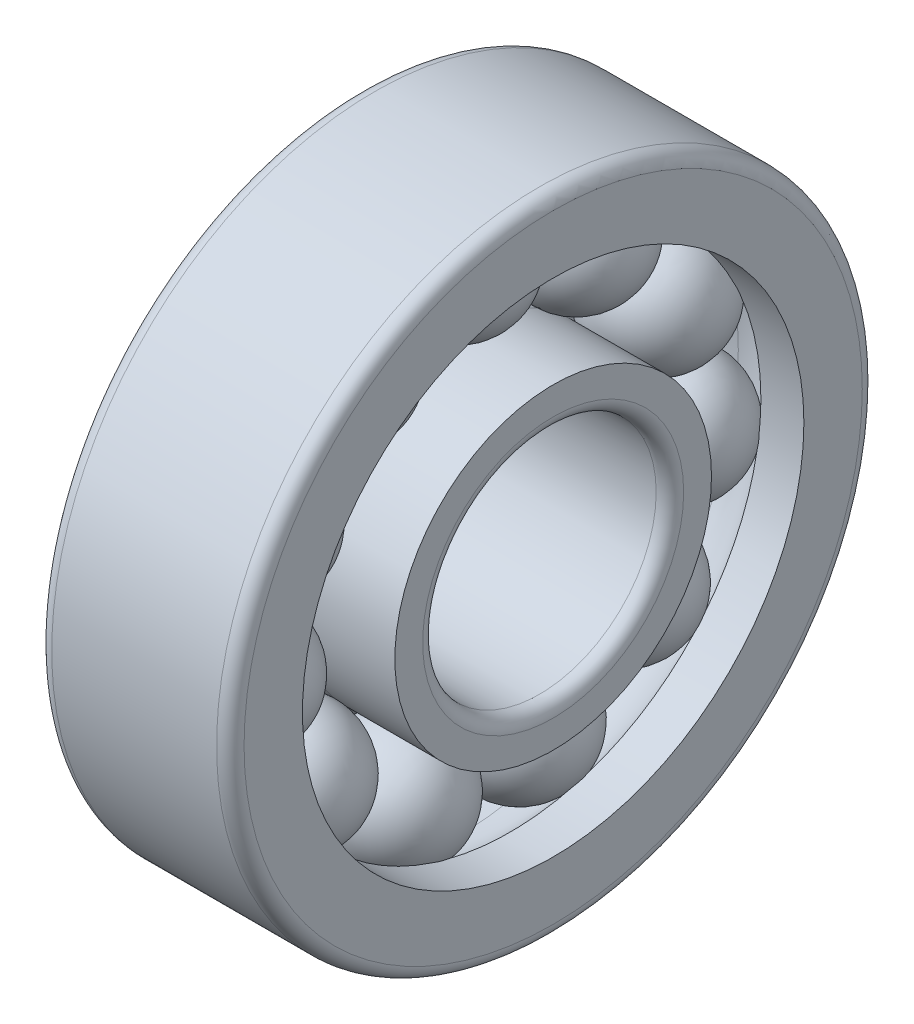
SolidWorks part; units mm, degrees
ref_plane "Plane1" through (0, 0, 0) normal (0, 0, 1) x (1, 0, 0)
ref_plane "Plane2" through (0, 0, 0) normal (0, 1, 0) x (1, 0, 0)
ref_plane "Plane3" through (0, 0, 0) normal (1, 0, 0) x (0, 0, -1)
sketch "Clipboard" plane through (0, 0, 0) normal (0, 0, 1) x (1, 0, 0)
  line L0 (-10, 0) -> (10, 0) construction
  line L1 (0, 0) -> (21.9499, -4.2666)
  line L2 (0, 0) -> (15.9976, -0.2792)
  line L3 (0, 0) -> (22.3573, 0.3902)
  line L4 (0, 0) -> (-22.3573, -0.3902)
  dimension "BallCLRad" = 16
sketch "CagSpiSke" plane through (0, 0, 0) normal (0, 0, 1) x (1, 0, 0)
  line L0 (1.125, 15.25) -> (1.125, 16.75)
  line L1 (1.125, 16.75) -> (-1.125, 16.75)
  line L2 (-1.125, 16.75) -> (-1.125, 15.25)
  line L3 (-1.125, 15.25) -> (1.125, 15.25)
  line L4 (-20.6375, 0) -> (20.6375, 0) construction
  line L5 (0, 0) -> (0, 23.7692) construction
  dimension "OD" = 33.5
  dimension "ID" = 30.5
revolve "CageSpine" add sketch "CagSpiSke" angle 0.001 about L4
ref_axis "Axis1" through (-50, 0, 0) along (1, 0, 0)
sketch "CagBalSke" plane through (0, 0, 0) normal (0, 0, 1) x (1, 0, 0)
  line L0 (-4.95, 16) -> (4.95, 16)
  line L1 (-1.905, 16) -> (1.905, 16) construction
  line L2 (-10, 0) -> (10, 0) construction
  line L3 (0, 0) -> (0, 24) construction
  arc A0 (4.95, 16) -> (-4.95, 16) centre (0, 16) cw
  dimension "BallCLRad" = 16
revolve "CageBall" [suppressed] add sketch "CagBalSke" angle 360 about L1 reverse direction yes
pattern_circular "CageBalls" [suppressed] count 11 every 32.727 about axis through (-50, 0, 0) along (1, 0, 0)
sketch "CagTrmODSke" plane through (0, 0, 0) normal (0, 0, 1) x (1, 0, 0)
  line L0 (4.951, 16.75) -> (4.951, 20.951)
  line L1 (4.951, 20.951) -> (-4.951, 20.951)
  line L2 (-4.951, 20.951) -> (-4.951, 16.75)
  line L3 (-4.951, 16.75) -> (4.951, 16.75)
  line L4 (-20.6375, 0) -> (20.6375, 0) construction
  line L5 (0, 0) -> (0, 25) construction
  dimension "Width" = 9.902
  dimension "ID" = 33.5
  dimension "OD" = 41.902
revolve "CageTrimOD" [suppressed] cut sketch "CagTrmODSke" angle 360 about L4 reverse direction yes
sketch "CagTrmIDSke" plane through (0, 0, 0) normal (0, 0, 1) x (1, 0, 0)
  line L0 (4.951, 11.051) -> (4.951, 15.25)
  line L1 (4.951, 15.25) -> (-4.951, 15.25)
  line L2 (-4.951, 15.25) -> (-4.951, 11.051)
  line L3 (-4.951, 11.051) -> (4.951, 11.051)
  line L4 (-20.6375, 0) -> (20.6375, 0) construction
  line L5 (0, 0) -> (0, 25) construction
  dimension "Width" = 9.902
  dimension "ID" = 22.102
  dimension "OD" = 30.5
revolve "CageTrimID" [suppressed] cut sketch "CagTrmIDSke" angle 360 about L4 reverse direction yes
sketch "BalSimSke" plane through (0, 0, 0) normal (0, 0, 1) x (1, 0, 0)
  line L0 (-10, 0) -> (10, 0) construction
  line L1 (-10, 16) -> (10, 16) construction
  line L2 (0, 0) -> (0, 23) construction
  circle A0 centre (0, 16) radius 4.5
  dimension "BallCLRad" = 16
  dimension "Ball_diameter" = 9
revolve "BallsSimplified" [suppressed] add sketch "BalSimSke" angle 360 about L0
sketch "BalDetSke" plane through (0, 0, 0) normal (0, 0, 1) x (1, 0, 0)
  line L0 (-4.5, 16) -> (4.5, 16)
  line L1 (-1.905, 16) -> (1.905, 16) construction
  line L2 (0, 0) -> (0, 25) construction
  arc A0 (4.5, 16) -> (-4.5, 16) centre (0, 16) cw
  dimension "BallCLRad" = 16
  dimension "Ball_diameter" = 9
revolve "BallDetailed" add sketch "BalDetSke" angle 360 about L1 reverse direction yes
sketch "InnRacSke" plane through (0, 0, 0) normal (0, 0, 1) x (1, 0, 0)
  line L0 (-3.8682, 13.75) -> (-7, 13.75)
  line L1 (-7, 13.75) -> (-7, 9.5)
  line L2 (-6, 8.5) -> (6, 8.5)
  line L3 (7, 9.5) -> (7, 11.525)
  line L4 (0, 11.525) -> (7, 11.525)
  line L5 (-20.6375, 0) -> (20.6375, 0) construction
  line L6 (0, 0) -> (0, 30) construction
  arc A0 (-7, 9.5) -> (-6, 8.5) centre (-6, 9.5) ccw
  arc A1 (6, 8.5) -> (7, 9.5) centre (6, 9.5) ccw
  arc A2 (0, 11.525) -> (-3.8682, 13.75) centre (0, 16) cw
  dimension "BallCLRad" = 16
  dimension "Fillet_radius" = 1
  dimension "Ball_diameter" = 8.95
  dimension "ID" = 17
  dimension "OD" = 27.5
  dimension "Width" = 14
revolve "InnerRace" add sketch "InnRacSke" angle 360 about L5 reverse direction yes
sketch "OutRacSke" plane through (0, 0, 0) normal (0, 0, 1) x (1, 0, 0)
  line L0 (0, 20.475) -> (-7, 20.475)
  line L1 (-7, 20.475) -> (-7, 22.5)
  line L2 (-6, 23.5) -> (6, 23.5)
  line L3 (7, 22.5) -> (7, 18.25)
  line L4 (7, 18.25) -> (3.8682, 18.25)
  line L5 (-20.6375, 0) -> (20.6375, 0) construction
  line L6 (0, 0) -> (0, 30) construction
  arc A0 (-7, 22.5) -> (-6, 23.5) centre (-6, 22.5) cw
  arc A1 (6, 23.5) -> (7, 22.5) centre (6, 22.5) cw
  arc A2 (3.8682, 18.25) -> (0, 20.475) centre (0, 16) ccw
  dimension "BallCLRad" = 16
  dimension "Fillet_radius" = 1
  dimension "Ball_diameter" = 8.95
  dimension "Width" = 14
revolve "OuterRace" add sketch "OutRacSke" angle 360 about L5 reverse direction yes
pattern_circular "BallsDetailed" count 11 every 32.727 about axis through (-50, 0, 0) along (1, 0, 0) of "BallDetailed"
other "Freeze***"
equation "\"BallCLRad@Clipboard\" = ( \"OD@OutRacSke\" + \"ID@InnRacSke\" ) / 4"
equation "\"BallCLRad@BalSimSke\" = \"BallCLRad@Clipboard\""
equation "\"BallCLRad@BalDetSke\" = \"BallCLRad@Clipboard\""
equation "\"BallCLRad@InnRacSke\" = \"BallCLRad@Clipboard\""
equation "\"BallCLRad@OutRacSke\" = \"BallCLRad@Clipboard\""
equation "\"Ball_diameter@InnRacSke\" = \"Ball_diameter@BalDetSke\" - 0.05"
equation "\"Ball_diameter@OutRacSke\" = \"Ball_diameter@BalDetSke\" - 0.05"
equation "\"Ball_diameter@BalSimSke\" = \"Ball_diameter@BalDetSke\""
equation "\"Width@OutRacSke\" = \"Width@InnRacSke\""
equation "\"Fillet_radius@OutRacSke\" = \"Fillet_radius@InnRacSke\""
equation "\"Max_count@Clipboard\" = int( 3.14159265 / atn(( \"Ball_diameter@BalDetSke\" / 2) / sqr( \"BallCLRad@Clipboard\"  *  \"BallCLRad@Clipboard\" - ( \"Ball_diameter@BalDetSke\" / 2) *  ( \"Ball_diameter@BalDetSke\" / 2))))"
equation "\"Max_count@Clipboard\" = ((sgn( \"Max_count@Clipboard\" - \"Count@Clipboard\" )-1)*( \"Max_count@Clipboard\" - \"Count@Clipboard\" ))/-2+ \"Count@Clipboard\""
equation "\"Count@BallsDetailed\" = int( \"Show_count@Clipboard\" ) "
equation "\"Count@BallsDetailed\" = ((sgn( \"Count@BallsDetailed\" - \"Max_count@Clipboard\" )-1)*( \"Count@BallsDetailed\" - \"Max_count@Clipboard\" ))/-2+ \"Max_count@Clipboard\""
equation "\"Count@BallsDetailed\" = ((sgn( \"Count@BallsDetailed\" - \"Min_count@Clipboard\" )+1)*( \"Count@BallsDetailed\" - \"Min_count@Clipboard\"))/2 +\"Min_count@Clipboard\""
equation "\"Angle@BallsDetailed\" = 360.0 / \"Max_count@Clipboard\""
equation "\"BallCLRad@CagBalSke\" = \"BallCLRad@Clipboard\""
equation "\"Count@CageBalls\" = \"Count@BallsDetailed\""
equation "\"Angle@CageBalls\" = \"Angle@BallsDetailed\""
equation "\"Angle@CageSpine\" =  \"Angle@CageBalls\" * ( \"Count@CageBalls\" -1 + int( \"Count@CageBalls\" / \"Max_count@Clipboard\" ) )  + 0.001 -  int( \"Count@CageBalls\" / \"Max_count@Clipboard\" ) * 0.001"
equation "\"Angle@CageSpine\" =  \"Angle@CageSpine\" * int( \"Min_count@Clipboard\" / 2) + int(1 / \"Min_count@Clipboard\")  * 0.001"
equation "\"CageWallOD@CagBalSke\" =  \"Ball_diameter@BalDetSke\" * 1.1"
equation "\"Thickness@CagSpiSke\" =  \"Ball_diameter@BalDetSke\" * 0.25"
equation "\"OD@CagTrmODSke\" = \"BallCLRad@Clipboard\" * 2 + \"CageWallOD@CagBalSke\" + 0.002"
equation "\"ID@CagTrmODSke\" = \"BallCLRad@Clipboard\" * 2 + \"Ball_diameter@BalDetSke\" / 6"
equation "\"OD@CagTrmIDSke\" = \"BallCLRad@Clipboard\" * 2 - \"Ball_diameter@BalDetSke\" / 6"
equation "\"ID@CagTrmIDSke\" = \"BallCLRad@Clipboard\" * 2 - \"CageWallOD@CagBalSke\" + 0.002"
equation "\"OD@CagSpiSke\" = \"ID@CagTrmODSke\""
equation "\"ID@CagSpiSke\" = \"OD@CagTrmIDSke\""
equation "\"Width@CagTrmODSke\" = \"CageWallOD@CagBalSke\" + 0.002"
equation "\"Width@CagTrmIDSke\" = \"CageWallOD@CagBalSke\" + 0.002"
